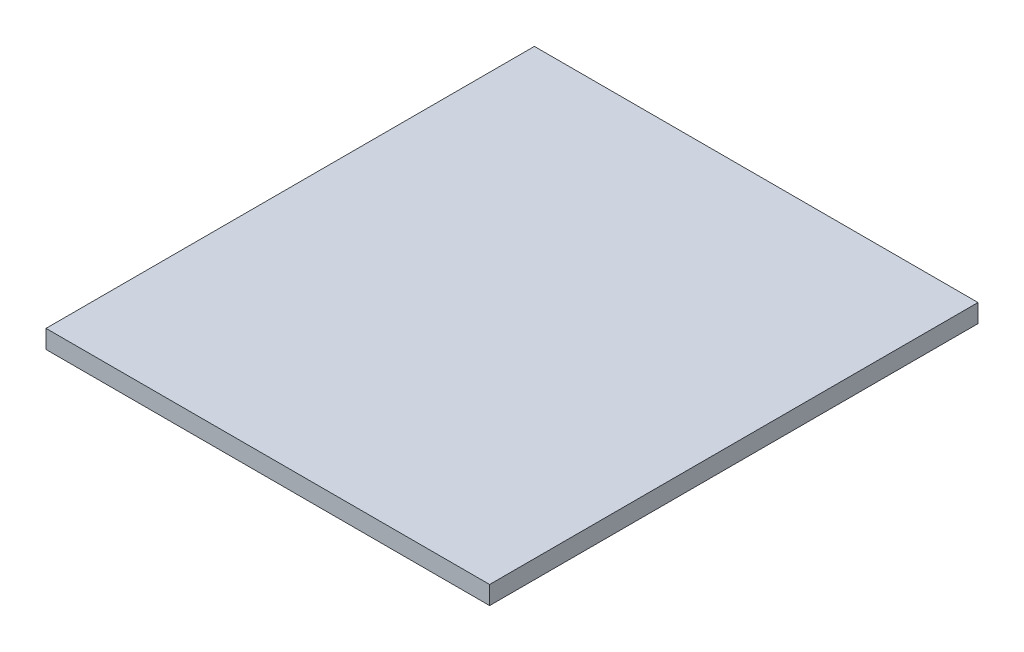
SolidWorks part; units mm, degrees
material "Perspex (TM) GS Acrylic Cast Sheet"
ref_plane "Front Plane" through (0, 0, 0) normal (0, 0, 1) x (1, 0, 0)
ref_plane "Top Plane" through (0, 0, 0) normal (0, 1, 0) x (1, 0, 0)
ref_plane "Right Plane" through (0, 0, 0) normal (1, 0, 0) x (0, 0, -1)
sketch "Sketch1" plane through (0, 0, 0) normal (0, 1, 0) x (1, 0, 0)
  line L1 (-109, -120) -> (109, -120)
  line L2 (-109, -120) -> (-109, 120)
  line L3 (-109, 120) -> (109, 120)
  line L4 (109, -120) -> (109, 120)
  line L5 (-109, -120) -> (109, 120) construction
  line L6 (-109, 120) -> (109, -120) construction
  point P0 (0, 0)
  dimension "D2" = 240
  dimension "D1" = 218
extrude "Boss-Extrude1" add sketch "Sketch1" along normal blind 9
equation "\"PCLength\"= 145mm'Length across I/O from PS to GPU"
equation "\"PCWidth\"= 340mm'Distance of longest part parallel to GPU(ussually GPU)"
equation "\"PCHeight\"= 180mm'Tallest point with mobo laying flat"
equation "\"WallThickness\"= 9mm'Thickness of each outer tank wall"
equation "\"ThermoBarrierThickness\"= 6mm'Thickness of barrier between hot side and cold side"
equation "\"HotSideGap\"= 36mm'Space in the hot side for a pump"
equation "\"PCClearance\"= 40mm'Clearance from top of tank to top of PC"
equation "\"RadiatorHeight\"= 277.37mm'Final Height from ground of radiators"
equation "\"D2@Sketch1\"=\"PCHeight\" + \"ThermoBarrierThickness\" + \"HotSideGap\" + (2 * \"WallThickness\")"
equation "\"D1@Boss-Extrude1\"=\"WallThickness\""
equation "\"D1@Sketch1\"=\"PCLength\" + (2 * \"WallThickness\") + \"AirflowGap\" + 30"
equation "\"AirflowGap\"= 25mm'Distance between radiators and tank for airflow"
equation "\"VolumeSubtraction\"= 230mm"
